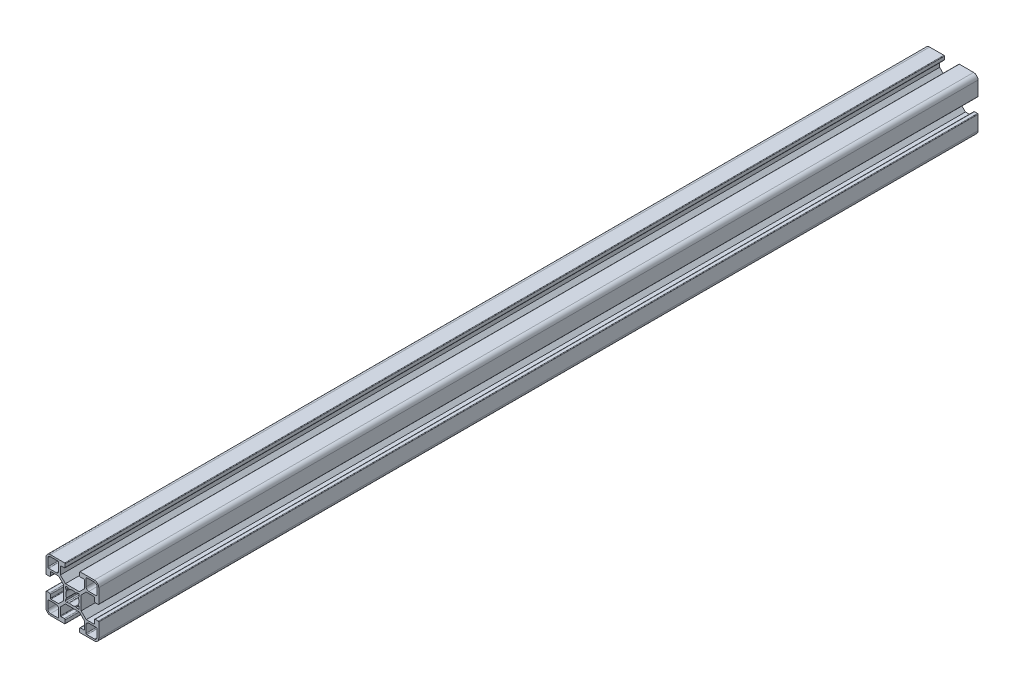
SolidWorks part; units mm, degrees
ref_plane "Front Plane" through (0, 0, 0) normal (0, 0, 1) x (1, 0, 0)
ref_plane "Top Plane" through (0, 0, 0) normal (0, 1, 0) x (1, 0, 0)
ref_plane "Right Plane" through (0, 0, 0) normal (1, 0, 0) x (0, 0, -1)
sketch "Sketch1" plane through (0, 0, 0) normal (0, 0, 1) x (1, 0, 0)
  line L0 (18.8789, 11.7141) -> (18.6573, 12.7569)
  line L1 (11.3427, 17.2431) -> (11.1211, 18.2859)
  line L2 (12.9949, 18.4193) -> (12.7569, 18.6573)
  line L3 (21.8, 7.1394) -> (18.9393, 10)
  line L4 (22.8607, 8.2) -> (20, 11.0607)
  line L5 (11.5807, 17.0051) -> (11.3427, 17.2431)
  line L6 (17.2431, 11.3427) -> (17.0051, 11.5806)
  line L7 (10, 18.9393) -> (7.1393, 21.8)
  line L8 (11.0607, 20) -> (8.2, 22.8607)
  line L9 (18.6573, 12.7569) -> (18.4193, 12.9948)
  line L10 (18.2859, 11.1211) -> (17.2431, 11.3427)
  line L11 (12.7569, 18.6573) -> (11.7141, 18.8789)
  line L12 (2.5, 0) -> (10.6, 0)
  line L13 (19.4, 0) -> (27.5, 0)
  line L14 (23.3, 1) -> (27.5, 1)
  line L15 (2.5, 1) -> (6.7, 1)
  line L16 (8.5, 2.5) -> (10.4, 2.5)
  line L17 (19.6, 2.5) -> (21.5, 2.5)
  line L18 (24.3, 7.2) -> (28.5, 7.2)
  line L19 (1.5, 7.2) -> (5.7, 7.2)
  line L20 (2.8, 8.2) -> (7.1393, 8.2)
  line L21 (22.8607, 8.2) -> (27.2, 8.2)
  line L22 (11.0607, 10) -> (18.9393, 10)
  line L23 (0.3, 10.9) -> (2, 10.9)
  line L24 (28, 10.9) -> (29.7, 10.9)
  line L25 (0.3, 19.1) -> (2, 19.1)
  line L26 (28, 19.1) -> (29.7, 19.1)
  line L27 (11.0607, 20) -> (18.9393, 20)
  line L28 (2.8, 21.8) -> (7.1393, 21.8)
  line L29 (22.8607, 21.8) -> (27.2, 21.8)
  line L30 (1.5, 22.8) -> (5.7, 22.8)
  line L31 (24.3, 22.8) -> (28.5, 22.8)
  line L32 (19.6, 27.5) -> (21.5, 27.5)
  line L33 (8.5, 27.5) -> (10.4, 27.5)
  line L34 (2.5, 29) -> (6.7, 29)
  line L35 (23.3, 29) -> (27.5, 29)
  line L36 (19.4, 30) -> (27.5, 30)
  line L37 (2.5, 30) -> (10.6, 30)
  line L38 (11.7141, 11.1211) -> (12.7569, 11.3427)
  line L39 (17.2431, 18.6573) -> (18.2859, 18.8789)
  line L40 (18.4194, 17.0051) -> (18.6573, 17.2431)
  line L41 (8.2, 7.1393) -> (11.0607, 10)
  line L42 (7.1393, 8.2) -> (10, 11.0607)
  line L43 (12.7569, 11.3427) -> (12.9949, 11.5806)
  line L44 (11.3427, 12.7569) -> (11.5807, 12.9949)
  line L45 (20, 18.9393) -> (22.8607, 21.8)
  line L46 (18.9393, 20) -> (21.8, 22.8607)
  line L47 (17.0051, 18.4193) -> (17.2431, 18.6573)
  line L48 (11.1211, 11.7141) -> (11.3427, 12.7569)
  line L49 (18.6573, 17.2431) -> (18.8789, 18.2859)
  line L50 (0, 19.4) -> (0, 27.5)
  line L51 (0, 2.5) -> (0, 10.6)
  line L52 (1, 23.3) -> (1, 27.5)
  line L53 (1, 2.5) -> (1, 6.7)
  line L54 (2.5, 8.5) -> (2.5, 10.4)
  line L55 (2.5, 19.6) -> (2.5, 21.5)
  line L56 (7.2, 24.3) -> (7.2, 28.5)
  line L57 (7.2, 1.5) -> (7.2, 5.7)
  line L58 (8.2, 2.8) -> (8.2, 7.1393)
  line L59 (8.2, 22.8607) -> (8.2, 27.2)
  line L60 (10, 11.0607) -> (10, 18.9393)
  line L61 (10.9, 0.3) -> (10.9, 2)
  line L62 (10.9, 28) -> (10.9, 29.7)
  line L63 (19.1, 0.3) -> (19.1, 2)
  line L64 (19.1, 28) -> (19.1, 29.7)
  line L65 (20, 11.0607) -> (20, 18.9393)
  line L66 (21.8, 2.8) -> (21.8, 7.1394)
  line L67 (21.8, 22.8607) -> (21.8, 27.2)
  line L68 (22.8, 24.3) -> (22.8, 28.5)
  line L69 (22.8, 1.5) -> (22.8, 5.7)
  line L70 (27.5, 8.5) -> (27.5, 10.4)
  line L71 (27.5, 19.6) -> (27.5, 21.5)
  line L72 (29, 23.3) -> (29, 27.5)
  line L73 (29, 2.5) -> (29, 6.7)
  line L74 (30, 2.5) -> (30, 10.6)
  line L75 (30, 19.4) -> (30, 27.5)
  arc A0 (0.3, 10.9) -> (0, 10.6) centre (0.3, 10.6) ccw
  arc A1 (0, 19.4) -> (0.3, 19.1) centre (0.3, 19.4) ccw
  arc A2 (1.5, 7.2) -> (1, 6.7) centre (1.5, 6.7) ccw
  arc A3 (1, 23.3) -> (1.5, 22.8) centre (1.5, 23.3) ccw
  arc A4 (2.5, 10.4) -> (2, 10.9) centre (2, 10.4) ccw
  arc A5 (2, 19.1) -> (2.5, 19.6) centre (2, 19.6) ccw
  arc A6 (1, 2.5) -> (2.5, 1) centre (2.5, 2.5) ccw
  arc A7 (0, 2.5) -> (2.5, 0) centre (2.5, 2.5) ccw
  arc A8 (2.5, 29) -> (1, 27.5) centre (2.5, 27.5) ccw
  arc A9 (2.5, 30) -> (0, 27.5) centre (2.5, 27.5) ccw
  arc A10 (2.5, 8.5) -> (2.8, 8.2) centre (2.8, 8.5) ccw
  arc A11 (2.8, 21.8) -> (2.5, 21.5) centre (2.8, 21.5) ccw
  arc A12 (7.2, 5.7) -> (5.7, 7.2) centre (5.7, 5.7) ccw
  arc A13 (5.7, 22.8) -> (7.2, 24.3) centre (5.7, 24.3) ccw
  arc A14 (6.7, 1) -> (7.2, 1.5) centre (6.7, 1.5) ccw
  arc A15 (7.2, 28.5) -> (6.7, 29) centre (6.7, 28.5) ccw
  arc A16 (8.2, 2.8) -> (8.5, 2.5) centre (8.5, 2.8) ccw
  arc A17 (8.5, 27.5) -> (8.2, 27.2) centre (8.5, 27.2) ccw
  arc A18 (10.9, 2) -> (10.4, 2.5) centre (10.4, 2) ccw
  arc A19 (10.4, 27.5) -> (10.9, 28) centre (10.4, 28) ccw
  arc A20 (10.6, 0) -> (10.9, 0.3) centre (10.6, 0.3) ccw
  arc A21 (10.9, 29.7) -> (10.6, 30) centre (10.6, 29.7) ccw
  arc A22 (11.5807, 12.9949) -> (11.6375, 13.3398) centre (11.3685, 13.207) ccw
  arc A23 (11.6375, 16.6602) -> (11.5807, 17.0051) centre (11.3685, 16.793) ccw
  arc A24 (11.1211, 11.7141) -> (11.7141, 11.1211) centre (11.6102, 11.6102) ccw
  arc A25 (11.7141, 18.8789) -> (11.1211, 18.2859) centre (11.6102, 18.3898) ccw
  arc A26 (13.3398, 11.6375) -> (12.9949, 11.5806) centre (13.207, 11.3685) ccw
  arc A27 (12.9949, 18.4193) -> (13.3398, 18.3625) centre (13.207, 18.6315) ccw
  arc A28 (11.6375, 16.6602) -> (11.6375, 13.3398) centre (15, 15) ccw
  arc A29 (16.6602, 18.3625) -> (13.3398, 18.3625) centre (15, 15) ccw
  arc A30 (18.3625, 13.3398) -> (18.3625, 16.6602) centre (15, 15) ccw
  arc A31 (13.3398, 11.6375) -> (16.6602, 11.6375) centre (15, 15) ccw
  arc A32 (17.0051, 11.5806) -> (16.6602, 11.6375) centre (16.793, 11.3685) ccw
  arc A33 (16.6602, 18.3625) -> (17.0051, 18.4193) centre (16.793, 18.6315) ccw
  arc A34 (18.2859, 11.1211) -> (18.8789, 11.7141) centre (18.3898, 11.6102) ccw
  arc A35 (18.8789, 18.2859) -> (18.2859, 18.8789) centre (18.3898, 18.3898) ccw
  arc A36 (18.3625, 13.3398) -> (18.4193, 12.9948) centre (18.6315, 13.207) ccw
  arc A37 (18.4194, 17.0051) -> (18.3625, 16.6602) centre (18.6315, 16.793) ccw
  arc A38 (19.1, 0.3) -> (19.4, 0) centre (19.4, 0.3) ccw
  arc A39 (19.4, 30) -> (19.1, 29.7) centre (19.4, 29.7) ccw
  arc A40 (19.6, 2.5) -> (19.1, 2) centre (19.6, 2) ccw
  arc A41 (19.1, 28) -> (19.6, 27.5) centre (19.6, 28) ccw
  arc A42 (21.5, 2.5) -> (21.8, 2.8) centre (21.5, 2.8) ccw
  arc A43 (21.8, 27.2) -> (21.5, 27.5) centre (21.5, 27.2) ccw
  arc A44 (22.8, 1.5) -> (23.3, 1) centre (23.3, 1.5) ccw
  arc A45 (23.3, 29) -> (22.8, 28.5) centre (23.3, 28.5) ccw
  arc A46 (24.3, 7.2) -> (22.8, 5.7) centre (24.3, 5.7) ccw
  arc A47 (22.8, 24.3) -> (24.3, 22.8) centre (24.3, 24.3) ccw
  arc A48 (27.2, 8.2) -> (27.5, 8.5) centre (27.2, 8.5) ccw
  arc A49 (27.5, 21.5) -> (27.2, 21.8) centre (27.2, 21.5) ccw
  arc A50 (27.5, 1) -> (29, 2.5) centre (27.5, 2.5) ccw
  arc A51 (27.5, 0) -> (30, 2.5) centre (27.5, 2.5) ccw
  arc A52 (29, 27.5) -> (27.5, 29) centre (27.5, 27.5) ccw
  arc A53 (30, 27.5) -> (27.5, 30) centre (27.5, 27.5) ccw
  arc A54 (28, 10.9) -> (27.5, 10.4) centre (28, 10.4) ccw
  arc A55 (27.5, 19.6) -> (28, 19.1) centre (28, 19.6) ccw
  arc A56 (29, 6.7) -> (28.5, 7.2) centre (28.5, 6.7) ccw
  arc A57 (28.5, 22.8) -> (29, 23.3) centre (28.5, 23.3) ccw
  arc A58 (30, 10.6) -> (29.7, 10.9) centre (29.7, 10.6) ccw
  arc A59 (29.7, 19.1) -> (30, 19.4) centre (29.7, 19.4) ccw
extrude "Boss-Extrude1" add sketch "Sketch1" along normal mid plane 500
equation "\"LENGTH\"=500"
